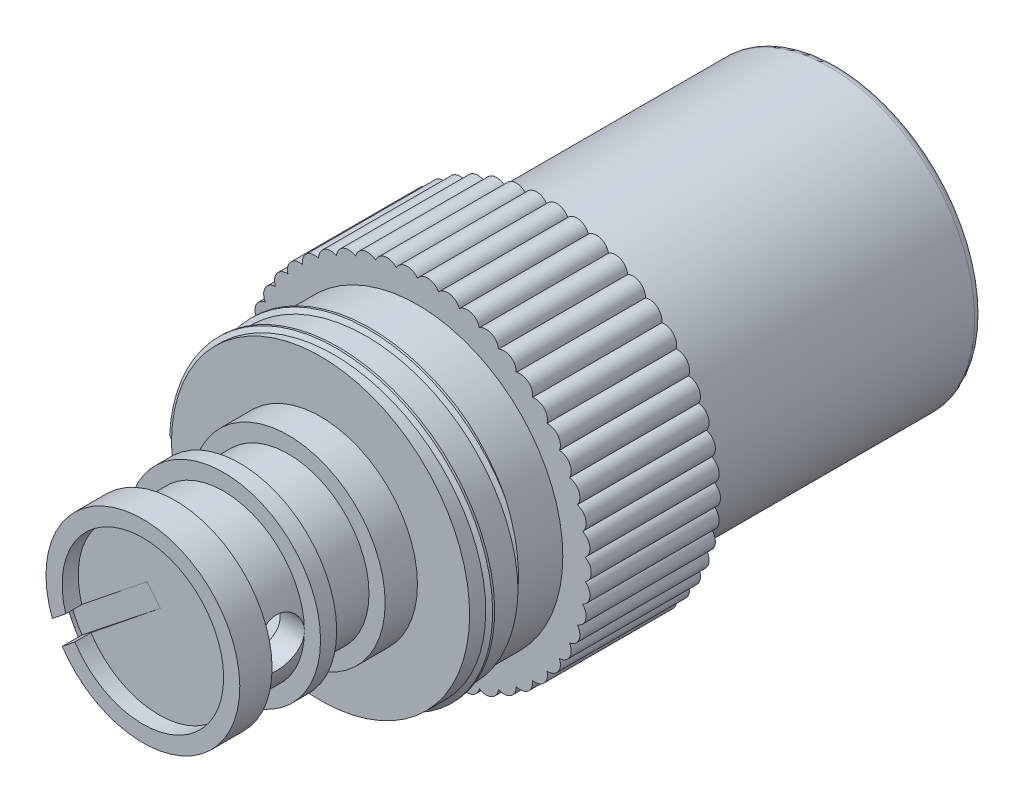
SolidWorks part; units mm, degrees
material "Brass"
ref_plane "Front Plane" through (0, 0, 0) normal (0, 0, 1) x (1, 0, 0)
ref_plane "Top Plane" through (0, 0, 0) normal (0, 1, 0) x (1, 0, 0)
ref_plane "Right Plane" through (0, 0, 0) normal (1, 0, 0) x (0, 0, -1)
sketch "Sketch18" plane through (0, 0, 0) normal (0, 0, 1) x (1, 0, 0)
  circle A0 centre (0, 0) radius 4.5
  dimension "D1" = 9
extrude "Boss-Extrude3" add sketch "Sketch18" along normal blind 9
sketch "Sketch19" plane through (0, 0, 9) normal (0, 0, 1) x (1, 0, 0)
  circle A0 centre (0, 0) radius 5
  dimension "D1" = 10
extrude "Boss-Extrude4" add sketch "Sketch19" along normal blind 4
sketch "Sketch20" plane through (0, 0, 9) normal (0, 0, -1) x (-1, 0, 0)
  arc A0 (-4.9856, 0.3797) -> (-4.9856, -0.3797) centre (-5, 0) ccw
  circle A1 centre (0, 0) radius 5 construction
  circle A2 centre (0, 0) radius 5
  circle M2 centre (0, 0) radius 5
  dimension "D1" = 0.76
extrude "Boss-Extrude5" add sketch "Sketch20" against normal blind 4 contours A0 M2 region at (5.1586, 0, 9)
pattern_circular "CirPattern3" count 50 over 360 about axis through (0, 0, 13) along (0, 0, -1) of "Boss-Extrude5"
sketch "Sketch21" plane through (0, 0, 13) normal (0, 0, 1) x (1, 0, 0)
  circle A0 centre (0, 0) radius 4.5
  dimension "D1" = 9
extrude "Boss-Extrude7" add sketch "Sketch21" along normal blind 3
sketch "Sketch24" plane through (0, 0, 16) normal (0, 0, 1) x (1, 0, 0)
  circle A0 centre (0, 0) radius 4.6147
  dimension "D1" = 9.2294
extrude "Boss-Extrude9" add sketch "Sketch24" against normal blind 1.5
thread "Thread4" pitch 0.25 method extrude trim with end face yes profile "Thread Profile8" start angle 1, offset 0, length 1.75, pitch 1, diameter 9.2294
ref_plane "Plane8" through (-4.614, 0.0805, 16) normal (0.0175, 0.9998, 0) x (0.9998, -0.0175, 0)
sketch "Thread Profile8" plane through (-4.614, 0.0805, 16) normal (0.0175, 0.9998, 0) x (0.9998, -0.0175, 0)
  line L0 (0, 0) -> (0, 0.25) construction
  line L11 (0, 0) -> (0, 0.2187)
  line L12 (0, 0.2187) -> (-0.1353, 0.1406)
  line L13 (-0.1353, 0.1406) -> (-0.1353, 0.0781)
  line L15 (-0.1353, 0.0781) -> (0, 0)
  line L17 (-0.1353, 0.1094) -> (0, 0.1094) construction
  point P2 (0, 0)
  dimension "Pitch" = 0.25
  dimension "Profile_Angle" = 60
  dimension "Profile_Land" = 0.0625
  dimension "Profile_Height" = 0.1353
sketch "Sketch29" plane through (0, 0, 16) normal (0, 0, 1) x (1, 0, 0)
  circle A0 centre (0, 0) radius 3
  dimension "D1" = 6
extrude "Boss-Extrude10" add sketch "Sketch29" along normal blind 1
sketch "Sketch30" plane through (0, 0, 17) normal (0, 0, 1) x (1, 0, 0)
  circle A0 centre (0, 0) radius 2.5
  dimension "D1" = 5
extrude "Boss-Extrude11" add sketch "Sketch30" along normal blind 1.5
sketch "Sketch31" plane through (0, 0, 18.5) normal (0, 0, 1) x (1, 0, 0)
  circle A0 centre (0, 0) radius 3
  dimension "D1" = 6
extrude "Boss-Extrude12" add sketch "Sketch31" along normal blind 0.5
sketch "Sketch32" plane through (0, 0, 19) normal (0, 0, 1) x (1, 0, 0)
  circle A0 centre (0, 0) radius 2.5
  dimension "D1" = 5
extrude "Boss-Extrude13" add sketch "Sketch32" along normal blind 1.5
sketch "Sketch33" plane through (0, 0, 20.5) normal (0, 0, 1) x (1, 0, 0)
  circle A0 centre (0, 0) radius 3
  dimension "D1" = 6
extrude "Boss-Extrude14" add sketch "Sketch33" along normal blind 1
sketch "Sketch34" plane through (0, 0, 0) normal (1, 0, 0) x (0, 0, -1)
  line L0 (-20.5, 0) -> (-19, 0) construction
  line L2 (-19, 3) -> (-19, -3) construction
  line L3 (-19, 3) -> (-19, -3) construction
  line L4 (-20.5, 3) -> (-20.5, -3) construction
  circle A0 centre (-19.75, 0) radius 0.75
  dimension "D1" = 1.5
extrude "Cut-Extrude1" cut sketch "Sketch34" against normal through all both and the other way through all
sketch "Sketch35" plane through (0, 0, 21.5) normal (0, 0, 1) x (1, 0, 0)
  circle A0 centre (0, 0) radius 2.5
  dimension "D1" = 5
extrude "Cut-Extrude2" cut sketch "Sketch35" against normal blind 0.4981
sketch "Sketch36" plane through (0, 0, 21.0019) normal (0, 0, 1) x (1, 0, 0)
  line L0 (0, 0) -> (-7.9833, -6.1934) construction
  line L1 (-7.9833, -6.1934) -> (6.2717, 4.8656) construction
  line L2 (-1.7564, -1.0657) -> (-2.7905, -1.8969)
  line L3 (-2.7905, -1.8969) -> (-3.2006, -1.3867)
  line L4 (-3.2006, -1.3867) -> (-2.1665, -0.5555)
  line L5 (-2.1665, -0.5555) -> (-1.7564, -1.0657)
extrude "Cut-Extrude3" cut sketch "Sketch36" along normal blind 0.5
sketch "Sketch37" plane through (0, 0, 21.0019) normal (0, 0, 1) x (1, 0, 0)
  line L0 (-2.3896, -0.7348) -> (-0.3682, 0.89)
  line L1 (-0.3682, 0.89) -> (0.042, 0.3798)
  line L2 (-2.1062, -1.3469) -> (0.042, 0.3798)
  line L3 (-2.4978, -1.6617) -> (-2.1062, -1.3469) construction
  line L4 (-2.1062, -1.3469) -> (-2.4978, -1.6617)
  line L5 (-2.3896, -0.7348) -> (-2.8036, -1.0676)
  arc A1 (-2.8036, -1.0676) -> (-2.4978, -1.6617) centre (0, 0) ccw
revolve "Cut-Revolve2" cut sketch "Sketch37" angle 2 about L1
sketch "Sketch40" plane through (0, 0, 0) normal (0, 0, -1) x (-1, 0, 0)
  circle A0 centre (0, 0) radius 4
  dimension "D1" = 8
extrude "Cut-Extrude4" cut sketch "Sketch40" against normal blind 11
fillet "Fillet2" 2 edges at (4.5, 0, 0) (-4, 0, 0) type full round first side face at (4.5, 0, 9) second side face at (-4, 0, 11) middle face at (-4, 0, 0)
sketch "Sketch41" plane through (0, 0, 11) normal (0, 0, -1) x (-1, 0, 0)
  circle A0 centre (0, 0) radius 2.75
  dimension "D1" = 5.5
extrude "Cut-Extrude5" cut sketch "Sketch41" against normal blind 3.5
sketch "Sketch42" plane through (0, 0, 14.5) normal (0, 0, -1) x (-1, 0, 0)
  circle A0 centre (0, 0) radius 1.75
  dimension "D1" = 3.5
extrude "Cut-Extrude6" cut sketch "Sketch42" against normal blind 5.75
ref_axis "Axis1" through (0, 0, 34.5127) along (0, 0, -1)
